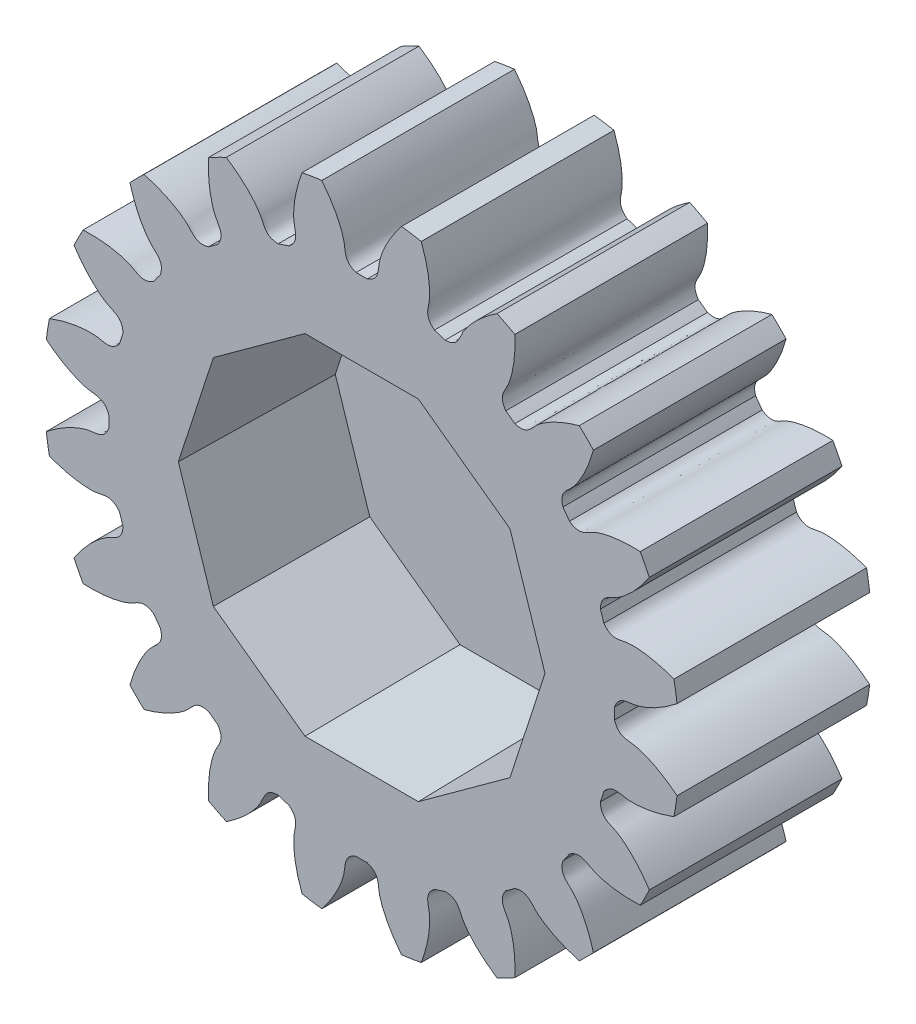
SolidWorks part; units mm, degrees
ref_plane "前视基准面" through (0, 0, 0) normal (0, 0, 1) x (1, 0, 0)
ref_plane "上视基准面" through (0, 0, 0) normal (0, 1, 0) x (1, 0, 0)
ref_plane "右视基准面" through (0, 0, 0) normal (1, 0, 0) x (0, 0, -1)
sketch "草图1" plane through (0, 0, 0) normal (0, 0, 1) x (1, 0, 0)
  circle A0 centre (0, 0) radius 16.5
extrude "凸台-拉伸1" add sketch "草图1" along normal blind 10
ref_axis "基准轴1" through (0, 0, -0.5) along (0, 0, 1)
sketch "草图2" plane through (0, 0, 0) normal (0, 0, 1) x (1, 0, 0)
  line L0 (0, 0) -> (0, 16.5) construction
  circle A0 centre (0, 0) radius 16.5 construction
  arc A1 (0.29, 13.1218) -> (-0.29, 13.1218) centre (0, 0) ccw
  arc A2 (4.7717, 18.7474) -> (-4.7717, 18.7474) centre (0, 0) ccw
  spline S0 degree 3 poles (0.29, 13.1218) (0.9168, 13.3402) (0.8356, 13.7807) (0.9193, 14.205) (0.9283, 14.2463) (0.9395, 14.293) (0.9529, 14.3448) (0.969, 14.4018) (0.9878, 14.4638) (1.0095, 14.5309) (1.0345, 14.6028) (1.0629, 14.6795) (1.0948, 14.7608) (1.1305, 14.8467) (1.1702, 14.9371) (1.2141, 15.0317) (1.2623, 15.1305) (1.315, 15.2334) (1.3725, 15.3401) (1.4349, 15.4506) (1.5023, 15.5646) (1.575, 15.6821) (1.653, 15.8029) (1.7366, 15.9267) (1.826, 16.0534) (1.9211, 16.1829) (2.0223, 16.3149) (2.1296, 16.4493) (2.2432, 16.5859) (2.3632, 16.7244) (2.4897, 16.8646) (2.6229, 17.0065) (2.7628, 17.1496) (2.9095, 17.2939) (3.0632, 17.4391) (3.224, 17.585) (3.3918, 17.7313) (3.567, 17.8779) (3.7493, 18.0245) (3.9391, 18.1709) (4.1363, 18.3167) (4.4122, 18.5125) (4.6259, 18.6545) (4.7717, 18.7474) knots 0 0 0 0 0.165916 0.170906 0.176664 0.183189 0.190482 0.198542 0.207371 0.216967 0.22733 0.238462 0.250361 0.263027 0.276462 0.290664 0.305634 0.321371 0.337876 0.355149 0.37319 0.391998 0.411574 0.431917 0.453028 0.474907 0.497554 0.520968 0.54515 0.570099 0.595817 0.622302 0.649554 0.677575 0.706363 0.735918 0.766242 0.797333 0.829191 0.861818 0.895212 0.929373 1 1 1 1
  spline S1 degree 3 poles (-0.29, 13.1218) (-0.9168, 13.3402) (-0.8356, 13.7807) (-0.9193, 14.205) (-0.9283, 14.2463) (-0.9395, 14.293) (-0.9529, 14.3448) (-0.969, 14.4018) (-0.9878, 14.4638) (-1.0095, 14.5309) (-1.0345, 14.6028) (-1.0629, 14.6795) (-1.0948, 14.7608) (-1.1305, 14.8467) (-1.1702, 14.9371) (-1.2141, 15.0317) (-1.2623, 15.1305) (-1.315, 15.2334) (-1.3725, 15.3401) (-1.4349, 15.4506) (-1.5023, 15.5646) (-1.575, 15.6821) (-1.653, 15.8029) (-1.7366, 15.9267) (-1.826, 16.0534) (-1.9211, 16.1829) (-2.0223, 16.3149) (-2.1296, 16.4493) (-2.2432, 16.5859) (-2.3632, 16.7244) (-2.4897, 16.8646) (-2.6229, 17.0065) (-2.7628, 17.1496) (-2.9095, 17.2939) (-3.0632, 17.4391) (-3.224, 17.585) (-3.3918, 17.7313) (-3.567, 17.8779) (-3.7493, 18.0245) (-3.9391, 18.1709) (-4.1363, 18.3167) (-4.4122, 18.5125) (-4.6259, 18.6545) (-4.7717, 18.7474) knots 0 0 0 0 0.165916 0.170906 0.176664 0.183189 0.190482 0.198542 0.207371 0.216967 0.22733 0.238462 0.250361 0.263027 0.276462 0.290664 0.305634 0.321371 0.337876 0.355149 0.37319 0.391998 0.411574 0.431917 0.453028 0.474907 0.497554 0.520968 0.54515 0.570099 0.595817 0.622302 0.649554 0.677575 0.706363 0.735918 0.766242 0.797333 0.829191 0.861818 0.895212 0.929373 1 1 1 1
extrude "切除-拉伸1" cut sketch "草图2" along normal through all
pattern_circular "阵列(圆周)1" count 20 every 18 about axis through (0, 0, -0.5) along (0, 0, 1) of "切除-拉伸1"
sketch "草图3" plane through (0, 0, 0) normal (0, 0, 1) x (1, 0, 0)
  circle A0 centre (0, 0) radius 15 construction
  dimension "Dn" = 30
sketch "草图4" plane through (0, 0, 10) normal (0, 0, 1) x (1, 0, 0)
  line L1 (9.5157, 0) -> (7.6984, 5.5932)
  line L2 (7.6984, 5.5932) -> (2.9405, 9.05)
  line L3 (2.9405, 9.05) -> (-2.9405, 9.05)
  line L4 (-2.9405, 9.05) -> (-7.6984, 5.5932)
  line L5 (-7.6984, 5.5932) -> (-9.5157, 0)
  line L6 (-9.5157, 0) -> (-7.6984, -5.5932)
  line L7 (-7.6984, -5.5932) -> (-2.9405, -9.05)
  line L8 (-2.9405, -9.05) -> (2.9405, -9.05)
  line L9 (2.9405, -9.05) -> (7.6984, -5.5932)
  line L10 (7.6984, -5.5932) -> (9.5157, 0)
  circle A0 centre (0, 0) radius 9.05 construction
  dimension "D1" = 18.1
extrude "切除-拉伸2" cut sketch "草图4" against normal blind 8 draft 1
sketch "草图5" plane through (0, 0, 0) normal (0, 0, -1) x (-1, 0, 0)
  line L0 (0, 0) -> (2.5812, 16.2969) construction
  arc A0 (3.0932, 16.2075) -> (2.0665, 16.3701) centre (0, 0) ccw construction
